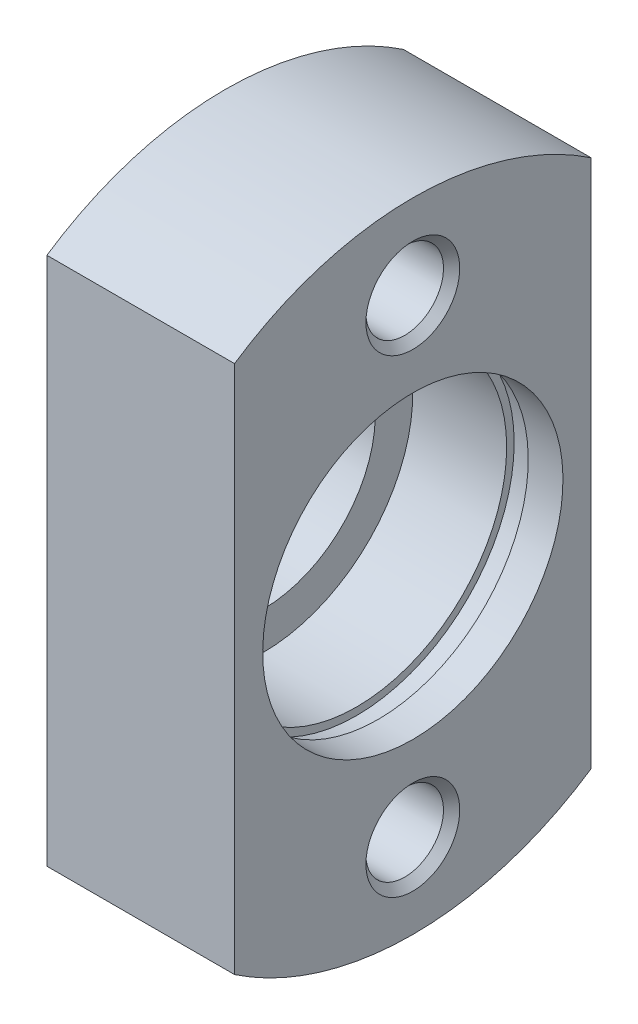
SolidWorks part; units mm, degrees
ref_plane "Front Plane" through (0, 0, 0) normal (0, 0, 1) x (1, 0, 0)
ref_plane "Top Plane" through (0, 0, 0) normal (0, 1, 0) x (1, 0, 0)
ref_plane "Right Plane" through (0, 0, 0) normal (1, 0, 0) x (0, 0, -1)
ref_plane "Plane1" through (0, 0, 0) normal (1, 0, 0) x (0, 0, -1)
sketch "Sketch1" plane through (0, 0, 0) normal (1, 0, 0) x (0, 0, -1)
  line L0 (9.5, -14.0979) -> (9.5, 14.0979)
  line L1 (-9.5, 14.0979) -> (-9.5, -14.0979)
  arc A0 (-9.5, -14.0979) -> (9.5, -14.0979) centre (0, 0) ccw
  arc A1 (9.5, 14.0979) -> (-9.5, 14.0979) centre (0, 0) ccw
extrude "Boss-Extrude1" add sketch "Sketch1" against normal blind 5 and the other way blind 5
ref_plane "Plane2" through (0, 0, 0) normal (0, 0, 1) x (1, 0, 0)
sketch "Sketch2" plane through (0, 0, 0) normal (0, 0, 1) x (1, 0, 0)
  line L0 (-5, 0) -> (-5, 6)
  line L1 (-5, 6) -> (-3, 6)
  line L2 (-3, 6) -> (-3, 8)
  line L3 (-3, 8) -> (5, 8)
  line L4 (5, 8) -> (5, 0)
  line L5 (5, 0) -> (-5, 0)
  line L6 (5, 0) -> (-5, 0) construction
revolve "Cut-Revolve1" cut sketch "Sketch2" angle 360 about L6 reverse direction yes
ref_plane "Plane3" through (0, 0, 0) normal (0, 0, 1) x (1, 0, 0)
sketch "Sketch3" plane through (0, 0, 0) normal (0, 0, 1) x (1, 0, 0)
  line L0 (2, 0) -> (2, 8.4)
  line L1 (2, 8.4) -> (3.15, 8.4)
  line L2 (3.15, 8.4) -> (3.15, 0)
  line L3 (3.15, 0) -> (2, 0)
  line L4 (3.15, 0) -> (2, 0) construction
revolve "Cut-Revolve2" cut sketch "Sketch3" angle 360 about L4 reverse direction yes
ref_plane "Plane4" through (0, 0, 0) normal (0, 0, 1) x (1, 0, 0)
sketch "Sketch4" plane through (0, 0, 0) normal (0, 0, 1) x (1, 0, 0)
  line L0 (-5, -12.5) -> (-5, -10)
  line L1 (-5, -10) -> (-4.567, -10.433)
  line L2 (-4.567, -10.433) -> (4.567, -10.433)
  line L3 (4.567, -10.433) -> (5, -10)
  line L4 (5, -10) -> (5, -12.5)
  line L5 (5, -12.5) -> (-5, -12.5)
  line L6 (5, -12.5) -> (-5, -12.5) construction
revolve "Cut-Revolve3" cut sketch "Sketch4" angle 360 about L6 reverse direction yes
ref_plane "Plane5" through (0, 0, 0) normal (0, 0, 1) x (1, 0, 0)
sketch "Sketch5" plane through (0, 0, 0) normal (0, 0, 1) x (1, 0, 0)
  line L0 (-5, 12.5) -> (-5, 15)
  line L1 (-5, 15) -> (-4.567, 14.567)
  line L2 (-4.567, 14.567) -> (4.567, 14.567)
  line L3 (4.567, 14.567) -> (5, 15)
  line L4 (5, 15) -> (5, 12.5)
  line L5 (5, 12.5) -> (-5, 12.5)
  line L6 (5, 12.5) -> (-5, 12.5) construction
revolve "Cut-Revolve4" cut sketch "Sketch5" angle 360 about L6 reverse direction yes
